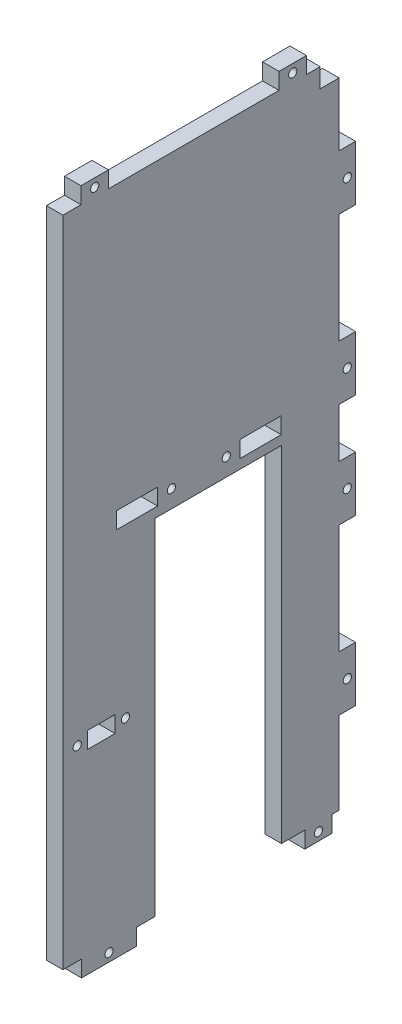
SolidWorks part; units mm, degrees
ref_plane "Plan de face" through (0, 0, 0) normal (0, 0, 1) x (1, 0, 0)
ref_plane "Plan de dessus" through (0, 0, 0) normal (0, 1, 0) x (1, 0, 0)
ref_plane "Plan de droite" through (0, 0, 0) normal (1, 0, 0) x (0, 0, -1)
sketch "Esquisse1" plane through (0, 0, 0) normal (1, 0, 0) x (0, 0, -1)
  line L0 (97.1531, 0) -> (-102.2664, 0) construction
  line L1 (-50.29, 119) -> (50.29, 119)
  line L2 (-50.29, 119) -> (-50.29, -119)
  line L3 (-50.29, -119) -> (50.29, -119)
  line L4 (50.29, 119) -> (50.29, -119)
  line L5 (0, 172.7153) -> (0, -236.1933) construction
  line L7 (-41.29, -48) -> (-31.29, -48)
  line L8 (-41.29, -48) -> (-41.29, -54)
  line L9 (-41.29, -54) -> (-31.29, -54)
  line L10 (-31.29, -48) -> (-31.29, -54)
  line L15 (-30.795, 16) -> (-15.795, 16)
  line L16 (-30.795, 16) -> (-30.795, 10)
  line L17 (-30.795, 10) -> (-15.795, 10)
  line L18 (-15.795, 16) -> (-15.795, 10)
  line L19 (14.205, 16) -> (29.205, 16)
  line L20 (14.205, 16) -> (14.205, 10)
  line L21 (14.205, 10) -> (29.205, 10)
  line L22 (29.205, 16) -> (29.205, 10)
  dimension "D1" = 238
  dimension "D2" = 100.58
  dimension "D4" = 119
  dimension "D13" = 15
  dimension "D14" = 15
  dimension "D15" = 30
  dimension "D16" = 6
  dimension "D17" = 6
  dimension "D3" = 50.29
  dimension "D6" = 19.495
  dimension "D7" = 9
  dimension "D8" = 167
  dimension "D9" = 6
  dimension "D10" = 10
  dimension "D5" = 103
extrude "Boss.-Extru.1" add sketch "Esquisse1" along normal blind 6
sketch "Esquisse3" plane through (6, 0, 0) normal (1, 0, 0) x (0, 0, -1)
  line L0 (-50.29, -119) -> (50.29, -119) construction
  line L1 (-43.5, -119) -> (-23.5, -119)
  line L2 (-43.5, -119) -> (-43.5, -125)
  line L3 (-43.5, -125) -> (-23.5, -125)
  line L4 (-23.5, -119) -> (-23.5, -125)
  line L5 (245.3741, 0) -> (-166.5298, 0) construction
  line L6 (50.29, -119) -> (50.29, 119) construction
  line L7 (37.79, -119) -> (47.79, -119)
  line L8 (37.79, -119) -> (37.79, -125)
  line L9 (37.79, -125) -> (47.79, -125)
  line L10 (0, 208.6671) -> (0, -232.3841) construction
  line L12 (47.79, -119) -> (47.79, -125)
  line L13 (56.29, 29) -> (56.29, 9)
  line L14 (50.29, 9) -> (56.29, 9)
  line L15 (50.29, 29) -> (50.29, 9)
  line L16 (50.29, 29) -> (56.29, 29)
  line L17 (56.29, 89) -> (56.29, 69)
  line L18 (50.29, 69) -> (56.29, 69)
  line L19 (50.29, 89) -> (50.29, 69)
  line L20 (50.29, 89) -> (56.29, 89)
  line L21 (50.29, 119) -> (-50.29, 119) construction
  line L22 (50.29, -89) -> (56.29, -89)
  line L23 (50.29, -89) -> (50.29, -69)
  line L24 (50.29, -69) -> (56.29, -69)
  line L25 (56.29, -89) -> (56.29, -69)
  line L26 (50.29, -29) -> (56.29, -29)
  line L27 (50.29, -29) -> (50.29, -9)
  line L28 (50.29, -9) -> (56.29, -9)
  line L29 (0, -208.6671) -> (0, 232.3841) construction
  line L30 (-50.29, 119) -> (-50.29, -119) construction
  line L34 (50.29, -119) -> (50.29, 119) construction
  line L35 (56.29, -29) -> (56.29, -9)
  line L36 (38.41, 119) -> (28.41, 119)
  line L37 (38.41, 119) -> (38.41, 125)
  line L38 (38.41, 125) -> (28.41, 125)
  line L39 (28.41, 119) -> (28.41, 125)
  line L40 (-50.29, 119) -> (-50.29, -119) construction
  line L41 (-33.71, 119) -> (-43.71, 119)
  line L42 (-33.71, 119) -> (-33.71, 125)
  line L43 (-33.71, 125) -> (-43.71, 125)
  line L44 (-43.71, 119) -> (-43.71, 125)
  dimension "D2" = 20
  dimension "D3" = 6
  dimension "D4" = 10
  dimension "D5" = 6.79
  dimension "D6" = 6
  dimension "D7" = 6
  dimension "D8" = 20
  dimension "D9" = 6
  dimension "D10" = 20
  dimension "D11" = 2.5
  dimension "D14" = 30
  dimension "D15" = 40
  dimension "D16" = 6
  dimension "D17" = 10
  dimension "D18" = 11.88
  dimension "D19" = 6.58
  dimension "D20" = 10
  dimension "D21" = 6
extrude "Boss.-Extru.5" add sketch "Esquisse3" against normal blind 6
sketch "Esquisse6" plane through (6, 0, 0) normal (1, 0, 0) x (0, 0, -1)
  line L0 (-23.5, -119) -> (37.79, -119) construction
  line L1 (-16.71, -119) -> (29.29, -119)
  line L2 (-16.71, -119) -> (-16.71, 6.59)
  line L3 (-16.71, 6.59) -> (29.29, 6.59)
  line L4 (29.29, -119) -> (29.29, 6.59)
  line L5 (50.29, -69) -> (50.29, -29) construction
  line L8 (28.41, 119) -> (-33.71, 119) construction
  dimension "D1" = 46
  dimension "D2" = 112.41
  dimension "D3" = 21
extrude "Enlèv. mat.-Extru.2" cut sketch "Esquisse6" against normal blind 6
sketch "Esquisse7" plane through (0, 0, 0) normal (-1, 0, 0) x (0, 0, 1)
  line L1 (-50.29, 119) -> (-43.41, 119)
  line L2 (-50.29, 119) -> (-50.29, 112)
  line L3 (-50.29, 112) -> (-43.41, 112)
  line L4 (-43.41, 119) -> (-43.41, 112)
  dimension "D1" = 7
  dimension "D2" = 6.88
extrude "Enlèv. mat.-Extru.3" cut sketch "Esquisse7" against normal blind 6
sketch "Esquisse8" plane through (0, 0, 0) normal (-1, 0, 0) x (0, 0, 1)
  line L0 (-51.0214, 13) -> (44.3386, 13) construction
  line L1 (43.5, -125) -> (23.5, -125) construction
  line L4 (30.795, 10) -> (15.795, 10) construction
  line L5 (60.5401, -51) -> (10.4957, -51) construction
  line L6 (41.29, -48) -> (41.29, -54) construction
  line L7 (31.29, -54) -> (31.29, -48) construction
  line L8 (41.29, -54) -> (31.29, -54) construction
  line L9 (53.2872, 122) -> (-67.0711, 122) construction
  line L10 (33.71, 125) -> (43.71, 125) construction
  line L11 (-28.41, 125) -> (-28.41, 119) construction
  line L12 (33.71, 119) -> (33.71, 125) construction
  line L13 (-67.0711, -122) -> (72.8873, -122) construction
  line L14 (15.795, 10) -> (15.795, 16) construction
  line L15 (-14.205, 16) -> (-14.205, 10) construction
  line L16 (-37.79, -119) -> (-37.79, -125) construction
  line L17 (23.5, -125) -> (23.5, -119) construction
  line L18 (-53.29, 135.0788) -> (-53.29, -173.0788) construction
  line L19 (-56.29, 69) -> (-56.29, 89) construction
  line L21 (-56.29, -69) -> (-50.29, -69) construction
  line L22 (-50.29, 9) -> (-56.29, 9) construction
  line L23 (-56.29, 89) -> (-50.29, 89) construction
  circle A1 centre (-9.205, 13) radius 1.5
  circle A2 centre (10.795, 13) radius 1.5
  circle A4 centre (27.5, -51) radius 1.5
  circle A5 centre (45.08, -51) radius 1.5
  circle A6 centre (38.71, 122) radius 1.5
  circle A7 centre (-33.41, 122) radius 1.5
  circle A8 centre (33.5, -122) radius 1.5
  circle A9 centre (-53.29, 79) radius 1.5
  circle A10 centre (-42.79, -122) radius 1.5
  circle A11 centre (-53.29, 19) radius 1.5
  circle A12 centre (-53.29, -79) radius 1.5
  circle A13 centre (-53.29, -19) radius 1.5
  point P8 (23.295, 10)
  dimension "D1" = 3
  dimension "D2" = 3
  dimension "D4" = 3
  dimension "D5" = 3
  dimension "D6" = 5
  dimension "D7" = 5
  dimension "D9" = 3
  dimension "D10" = 3
  dimension "D15" = 3
  dimension "D16" = 3
  dimension "D17" = 5
  dimension "D18" = 5
  dimension "D20" = 3
  dimension "D21" = 3
  dimension "D22" = 3
  dimension "D23" = 3
  dimension "D24" = 5
  dimension "D25" = 10
  dimension "D26" = 3
  dimension "D27" = 3
  dimension "D28" = 3
  dimension "D29" = 10
  dimension "D31" = 10
  dimension "D32" = 10
  dimension "D11" = 3.79
  dimension "D12" = 3.79
  dimension "D13" = 3
  dimension "D14" = 3
  dimension "D30" = 10
extrude "Enlèv. mat.-Extru.4" cut sketch "Esquisse8" against normal blind 6
equation "\"D3@Esquisse1\"=\"D2@Esquisse1\"/2"
equation "\"D4@Esquisse1\"=\"D1@Esquisse1\"/2"
